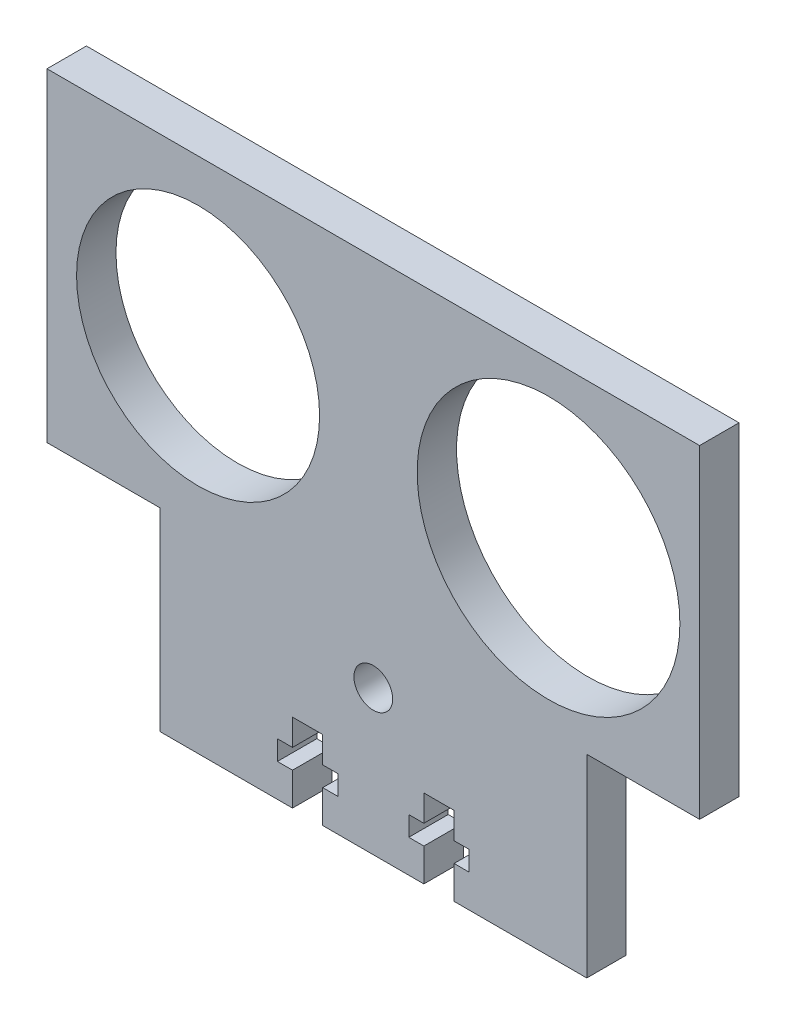
SolidWorks part; units mm, degrees
material "ABS"
ref_plane "Front Plane" through (0, 0, 0) normal (0, 0, 1) x (1, 0, 0)
ref_plane "Top Plane" through (0, 0, 0) normal (0, 1, 0) x (1, 0, 0)
ref_plane "Right Plane" through (0, 0, 0) normal (1, 0, 0) x (0, 0, -1)
sketch "Sketch1" plane through (0, 0, 0) normal (0, 0, 1) x (1, 0, 0)
  line L0 (0, 0) -> (-26.6757, 31.7908) construction
  line L1 (0, 0) -> (0, 56.7908) construction
  line L2 (-32.5, 7.5) -> (-32.5, -22)
  line L3 (-32.5, -22) -> (32.5, -22)
  line L4 (32.5, -22) -> (32.5, 7.5)
  line L5 (0, 0) -> (0, -22) construction
  line L6 (0, 0) -> (26.6757, 31.7908) construction
  line L10 (-32.5, 7.5) -> (-49.6757, 7.5)
  line L11 (-49.6757, 7.5) -> (-49.6757, 56.7908)
  line L12 (-49.6757, 56.7908) -> (49.6757, 56.7908)
  line L13 (49.6757, 56.7908) -> (49.6757, 7.5)
  line L14 (49.6757, 7.5) -> (32.5, 7.5)
  circle A0 centre (0, 0) radius 2.95
  circle A1 centre (26.6757, 31.7908) radius 20
  circle A2 centre (-26.6757, 31.7908) radius 18.5
  dimension "D1" = 5.9
  dimension "D9" = 37
  dimension "D11" = 40
  dimension "D2" = 41.5
  dimension "D4" = 40
  dimension "D5" = 22
  dimension "D6" = 65
  dimension "D3" = 23
  dimension "D7" = 25
  dimension "D8" = 29.5
  dimension "D10" = 40
extrude "Boss-Extrude1" add sketch "Sketch1" along normal blind 6
sketch "Sketch3" plane through (0, 0, 6) normal (0, 0, 1) x (1, 0, 0)
  line L0 (-32.5, -22) -> (32.5, -22) construction
  line L1 (-12.3, -22) -> (-7.7, -22)
  line L2 (-12.3, -22) -> (-12.3, -17)
  line L3 (-12.3, -10) -> (-7.7, -10)
  line L4 (-7.7, -22) -> (-7.7, -17)
  line L5 (0, 0) -> (0, -22) construction
  line L6 (-7.7, -14) -> (-5.4, -14)
  line L7 (-14.6, -14) -> (-12.3, -14)
  line L8 (-14.6, -14) -> (-14.6, -17)
  line L9 (-14.6, -17) -> (-12.3, -17)
  line L10 (-5.4, -14) -> (-5.4, -17)
  line L11 (-12.3, -14) -> (-12.3, -10)
  line L12 (-7.7, -17) -> (-5.4, -17)
  line L13 (-7.7, -14) -> (-7.7, -10)
  line L14 (7.7, -14) -> (7.7, -10)
  line L15 (7.7, -17) -> (5.4, -17)
  line L16 (12.3, -14) -> (12.3, -10)
  line L17 (5.4, -14) -> (5.4, -17)
  line L18 (14.6, -17) -> (12.3, -17)
  line L19 (14.6, -14) -> (14.6, -17)
  line L20 (14.6, -14) -> (12.3, -14)
  line L21 (7.7, -14) -> (5.4, -14)
  line L22 (7.7, -22) -> (7.7, -17)
  line L23 (12.3, -10) -> (7.7, -10)
  line L24 (12.3, -22) -> (12.3, -17)
  line L25 (12.3, -22) -> (7.7, -22)
  point P6 (-10, -10)
  point P18 (-13.45, -17)
  dimension "D1" = 4.6
  dimension "D2" = 10
  dimension "D3" = 12
  dimension "D4" = 9.2
  dimension "D5" = 3
  dimension "D6" = 5
extrude "Cut-Extrude2" cut sketch "Sketch3" against normal through all
equation "\"smallPulleyTeeth\"= 30"
equation "\"largePulleyTeeth\"= 30"
equation "\"eighthThick\"= 3.0mm"
equation "\"sixteenthThick\"= 1.7mm"
equation "\"quarterThick\"=6.0mm"
equation "\"OD\"= 145mm"
equation "\"puckAngle\"= 60.5deg"
equation "\"puckDiam\"= 76.5mm"
equation "\"axlePress\"= 5.9mm"
equation "\"D1@Sketch1\"=\"axlePress\""
equation "\"D1@Boss-Extrude1\"=\"quarterThick\""
equation "\"press\"= 0.2mm"
equation "\"wheelClear\"= 0.3mm"
equation "\"10-32clear\"= 4.8mm"
equation "\"D1@Sketch3\"=\"10-32clear\"-\"press\""
equation "\"6-32clear\"= 3.3mm"
equation "\"8-32clear\"= 4.0mm"
equation "\"wheelHeight\"= 22mm"
equation "\"D5@Sketch1\"=\"wheelHeight\""
equation "\"4-40clear\"= 3.0mm"
equation "\"wheelWell\"= 65mm"
equation "\"D6@Sketch1\"=\"wheelWell\""
equation "\"D8@Sketch1\"=\"eighthThick\"*10-0.5"
